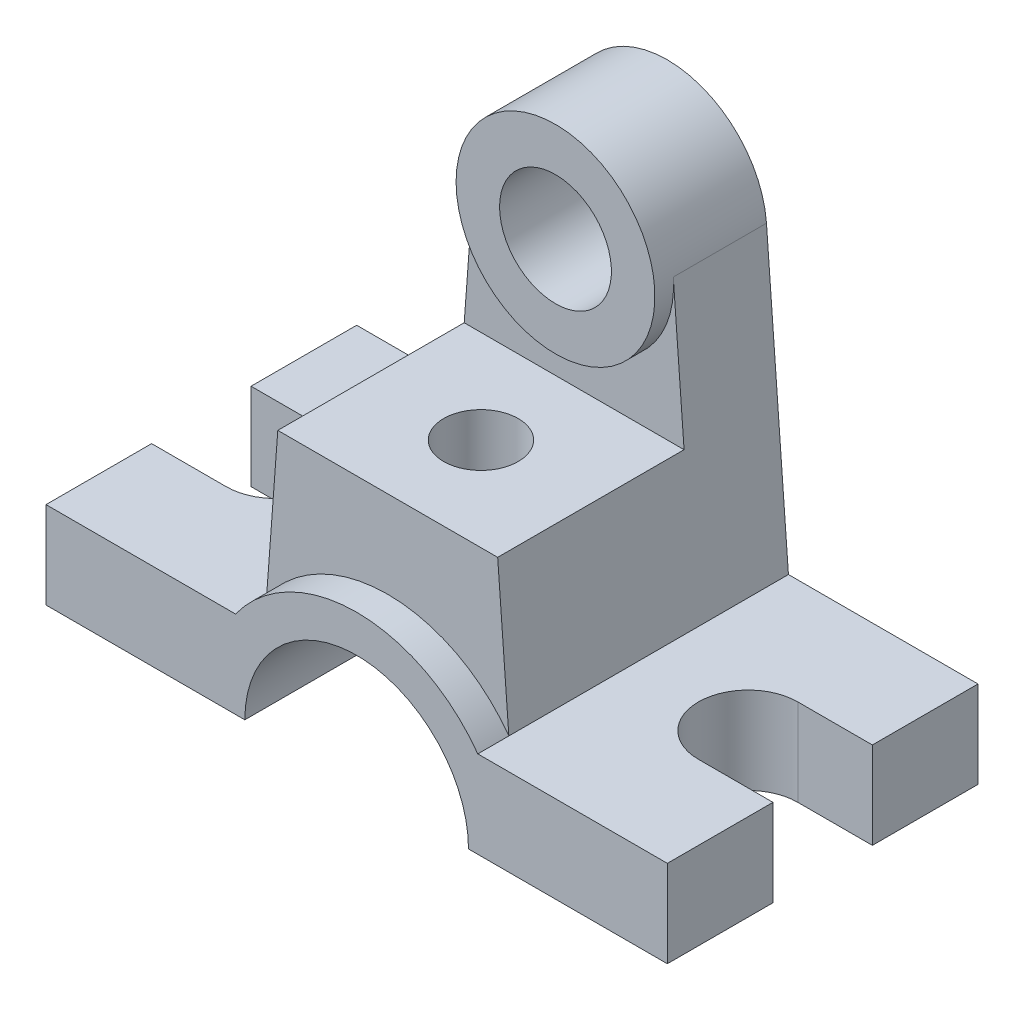
SolidWorks part; units mm, degrees
ref_plane "前视基准面" through (0, 0, 0) normal (0, 0, 1) x (1, 0, 0)
ref_plane "上视基准面" through (0, 0, 0) normal (0, 1, 0) x (1, 0, 0)
ref_plane "右视基准面" through (0, 0, 0) normal (1, 0, 0) x (0, 0, -1)
other "Configuration Table"
sketch "草图1" plane through (0, 0, 0) normal (0, 0, 1) x (1, 0, 0)
  line L0 (0, 0) -> (0, 32.271) construction
  line L1 (-50, 0) -> (-18, 0)
  line L2 (-50, 0) -> (-50, 14)
  line L3 (-50, 14) -> (-19.4936, 14)
  line L6 (50, 14) -> (19.4936, 14)
  line L7 (50, 0) -> (50, 14)
  line L8 (50, 0) -> (18, 0)
  arc A0 (-18, 0) -> (18, 0) centre (0, 0) cw
  arc A1 (-19.4936, 14) -> (19.4936, 14) centre (0, 0) cw
  point P7 (20.1408, 13.0517)
  dimension "D1" = 24
  dimension "D2" = 18
  dimension "D3" = 14
  dimension "D4" = 100
extrude "凸台-拉伸1" add sketch "草图1" against normal blind 50
sketch "草图2" plane through (0, 14, 0) normal (0, 1, 0) x (1, 0, 0)
  line L0 (-62, 25) -> (-38, 25) construction
  line L1 (-50, 50) -> (-50, 0) construction
  line L2 (-62, 33) -> (-38, 33)
  line L3 (-62, 17) -> (-38, 17)
  line L4 (0, 37.4901) -> (0, 13.8724) construction
  line L5 (62, 25) -> (38, 25) construction
  line L6 (62, 33) -> (38, 33)
  line L7 (62, 17) -> (38, 17)
  arc A0 (-62, 33) -> (-62, 17) centre (-62, 25) ccw
  arc A1 (-38, 17) -> (-38, 33) centre (-38, 25) ccw
  arc A2 (62, 33) -> (62, 17) centre (62, 25) cw
  arc A3 (38, 17) -> (38, 33) centre (38, 25) cw
  point P4 (-50, 25)
  point P14 (50, 25)
  dimension "D1" = 8
  dimension "D2" = 76
extrude "切除-拉伸1" cut sketch "草图2" against normal through all
sketch "草图4" plane through (0, 0, -50) normal (0, 0, -1) x (-1, 0, 0)
  line L0 (0, 12.7462) -> (0, 54.3366) construction
  line L1 (-19.4936, 14) -> (-15.9552, 61.1962)
  line L2 (19.4936, 14) -> (15.9552, 61.1962)
  line L3 (-17.6943, 38) -> (17.6943, 38)
  arc A0 (19.4936, 14) -> (-19.4936, 14) centre (0, 0) ccw construction
  circle A1 centre (0, 60) radius 16
  circle A2 centre (0, 60) radius 9
  arc A3 (19.4936, 14) -> (-19.4936, 14) centre (0, 0) ccw
  arc M8 (19.4936, 14) -> (-19.4936, 14) centre (0, 0) ccw
  dimension "D2" = 32
  dimension "D3" = 18
  dimension "D1" = 60
  dimension "D4" = 22
extrude "凸台-拉伸2" add sketch "草图4" against normal blind 15 contours L0 L2 A1 M8 | A3 L0 A1 L1 region at (0, 29.2129, -50)
extrude "凸台-拉伸3" add sketch "草图4<3>" against normal blind 18 contours A1 A2 region at (0, 75.5475, -50)
sketch "草图4<3>" plane through (0, 0, -50) normal (0, 0, -1) x (-1, 0, 0) same geometry as "草图4"
extrude "凸台-拉伸4" add sketch "草图4<4>" against normal blind 15 contours L0 L3 L2 A1 | L3 L0 A1 L1 region at (10.3939, 43.6341, -50) region at (-10.3939, 43.6341, -50)
sketch "草图4<4>" plane through (0, 0, -50) normal (0, 0, -1) x (-1, 0, 0) same geometry as "草图4"
extrude "凸台-拉伸5" add sketch "草图4<5>" against normal blind 45 contours L0 L2 L3 M8 | A3 L0 L3 L1 region at (10.0703, 29.2129, -50) region at (-10.0703, 29.2129, -50)
sketch "草图4<5>" plane through (0, 0, -50) normal (0, 0, -1) x (-1, 0, 0) same geometry as "草图4"
sketch "草图5" plane through (0, 38, 0) normal (0, 1, 0) x (1, 0, 0)
  line L0 (17.6943, 35) -> (-17.6943, 5) construction
  line L4 (17.6943, 5) -> (17.6943, 35)
  line L5 (17.6943, 35) -> (-17.6943, 35)
  line L6 (-17.6943, 35) -> (-17.6943, 5)
  line L7 (-17.6943, 5) -> (17.6943, 5)
  line L8 (17.6943, 5) -> (17.6943, 35)
  line L9 (17.6943, 35) -> (-17.6943, 35)
  line L10 (-17.6943, 35) -> (-17.6943, 5)
  line L11 (-17.6943, 5) -> (17.6943, 5)
  circle A0 centre (0, 20) radius 6
  point P4 (0, 20)
  dimension "D1" = 12
  dimension "D2" = 0
extrude "切除-拉伸2" cut sketch "草图5" against normal through all contours A0 L0 | L0 A0 region at (1.6467, 38, -18.0576) region at (-1.6467, 38, -21.9424)
